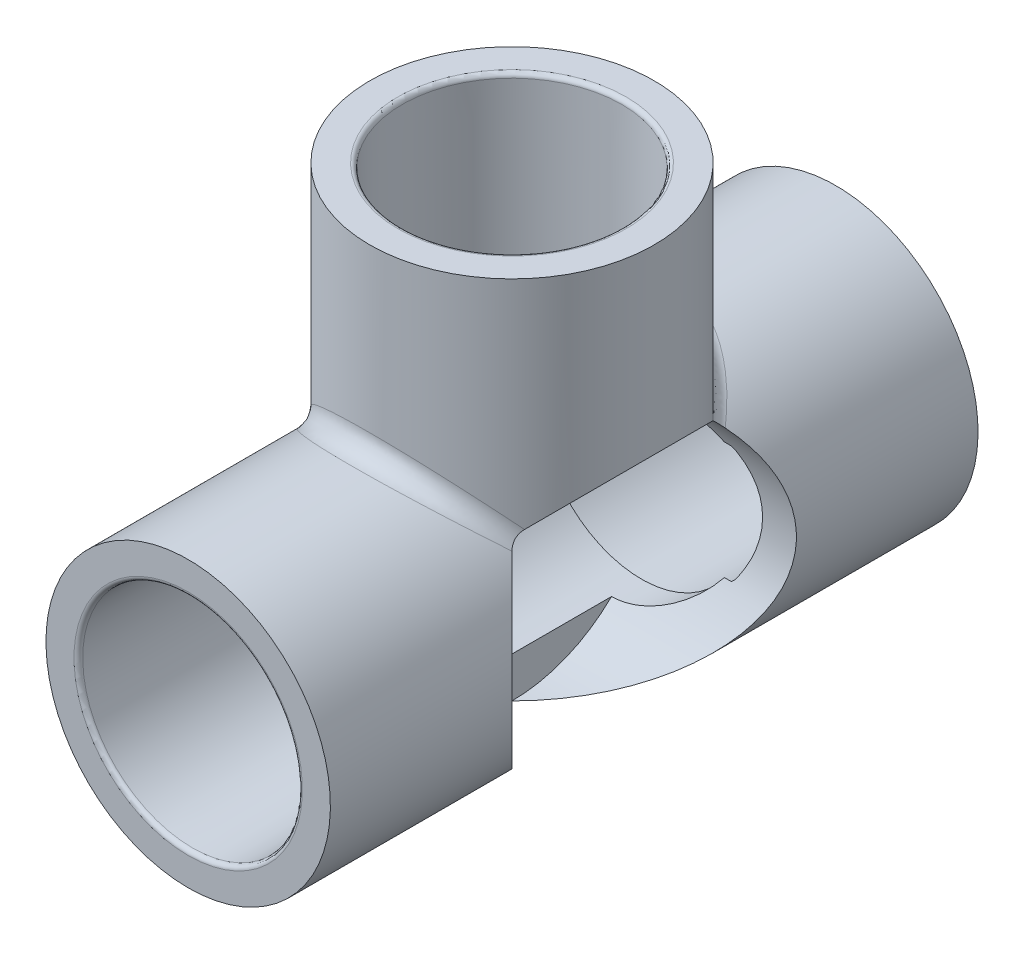
SolidWorks part; units mm, degrees
ref_plane "Front Plane" through (0, 0, 0) normal (0, 0, 1) x (1, 0, 0)
ref_plane "Top Plane" through (0, 0, 0) normal (0, 1, 0) x (1, 0, 0)
ref_plane "Right Plane" through (0, 0, 0) normal (1, 0, 0) x (0, 0, -1)
sketch "Sketch1" plane through (0, 0, 0) normal (1, 0, 0) x (0, 0, -1)
  line L0 (-31.75, 0) -> (31.75, 0) construction
  line L1 (-31.75, 0) -> (-31.75, -13.9446)
  line L2 (-31.75, -13.9446) -> (31.75, -13.9446)
  line L3 (31.75, -13.9446) -> (31.75, 0)
  line L4 (-31.75, -10.7696) -> (-12.7, -10.6172)
  line L5 (-12.7, -10.6172) -> (-12.7, -9.9568)
  line L6 (-12.7, -9.9568) -> (0, -9.9568)
  line L7 (0, -9.9568) -> (0, 0)
  line L8 (0, -9.9568) -> (0, -13.9446) construction
  point P2 (0, 0)
  dimension "Overall Length" = 63.5
  dimension "Diameter 1" = 21.5392
  dimension "Diameter 2" = 21.2344
  dimension "Wall 2" = 3.9878
  dimension "Wall 1" = 3.175
  dimension "Socket Depth" = 19.05
sketch "Sketch2" plane through (0, 0, 0) normal (1, 0, 0) x (0, 0, -1)
  line L0 (0, 0) -> (0, 31.75) construction
  line L1 (0, 31.75) -> (13.9446, 31.75)
  line L2 (13.9446, 31.75) -> (13.9446, 0)
  line L3 (-31.75, 0) -> (31.75, 0) construction
  line L4 (13.9446, 0) -> (0, 0)
  line L5 (10.7696, 31.75) -> (10.6172, 12.7)
  line L6 (10.6172, 12.7) -> (9.9695, 12.7)
  line L7 (9.9695, 12.7) -> (9.9695, 0)
  line L8 (-12.7, -9.9568) -> (0, -9.9568) construction
  dimension "Wall 3" = 3.175
  dimension "D1" = 21.5392
  dimension "D2" = 21.2344
  dimension "D3" = 19.05
  dimension "Diameter 3" = 19.939
sketch "Sketch3" plane through (0, 0, 0) normal (1, 0, 0) x (0, 0, -1)
  line L1 (-31.75, 0) -> (31.75, 0)
  line L2 (-31.75, 0) -> (-31.75, -13.9446)
  line L3 (-31.75, -13.9446) -> (31.75, -13.9446)
  line L4 (31.75, 0) -> (31.75, -13.9446)
revolve "Revolve1" add sketch "Sketch3" angle 360 about L1
sketch "Sketch4" plane through (0, 0, 0) normal (1, 0, 0) x (0, 0, -1)
  line L1 (0, 31.75) -> (13.9446, 31.75)
  line L2 (0, 31.75) -> (0, 0)
  line L3 (0, 0) -> (13.9446, 0)
  line L4 (13.9446, 31.75) -> (13.9446, 0)
revolve "Revolve2" add sketch "Sketch4" angle 360 about L2
sketch "Sketch5" plane through (0, 0, 0) normal (1, 0, 0) x (0, 0, -1)
  line L0 (-12.7, -9.9568) -> (0, -9.9568) construction
  line L1 (-12.7, -10.6172) -> (-12.7, -9.9568) construction
  line L2 (-31.75, -10.7696) -> (-12.7, -10.6172) construction
  line L3 (-12.7, -9.9568) -> (12.7, -9.9568)
  line L4 (-12.7, -10.6172) -> (-12.7, -9.9568)
  line L5 (-31.75, -10.7696) -> (-12.7, -10.6172)
  line L6 (-31.75, -10.7696) -> (-31.75, 0)
  line L7 (-31.75, 0) -> (31.75, 0)
  line L8 (0, 0) -> (0, -9.9568) construction
  line L9 (12.7, -10.6172) -> (12.7, -9.9568)
  line L10 (31.75, -10.7696) -> (12.7, -10.6172)
  line L11 (31.75, -10.7696) -> (31.75, 0)
revolve "Cut-Revolve1" cut sketch "Sketch5" angle 360 about L7
sketch "Sketch6" plane through (0, 0, 0) normal (1, 0, 0) x (0, 0, -1)
  line L0 (9.9695, 0) -> (9.9695, 12.7)
  line L1 (9.9695, 12.7) -> (10.6172, 12.7)
  line L2 (10.7696, 31.75) -> (10.6172, 12.7) construction
  line L3 (10.7696, 31.75) -> (10.6172, 12.7)
  line L4 (0, 0) -> (0, 31.75) construction
  line L5 (0, 0) -> (0, 31.75)
  line L6 (0, 31.75) -> (10.7696, 31.75)
  line L7 (0, 0) -> (9.9695, 0)
revolve "Cut-Revolve2" cut sketch "Sketch6" angle 360 about L5
fillet "Fillet1" radius 0.1619 3 edges at (0, -10.6172, -12.7) (0, 12.7, -10.6172) (0, -10.6172, 12.7)
fillet "Fillet2" radius 0.4308 3 edges at (0, -10.7696, -31.75) (0, 31.75, -10.7696) (0, -10.7696, 31.75)
fillet "Fillet3" radius 1.8536 2 edges at (0, 13.9446, 13.9446) (0, 13.9446, -13.9446)
sketch "Sketch7" plane through (0, 0, 0) normal (1, 0, 0) x (0, 0, -1)
  line L0 (-12.7, -9.9568) -> (0, -9.9568) construction
  line L1 (-12.7, -10.6172) -> (-12.7, -9.9568) construction
  line L2 (-31.75, -10.7696) -> (-12.7, -10.6172) construction
  line L3 (-12.7, -9.9568) -> (12.7, -9.9568)
  line L4 (-12.7, -10.6172) -> (-12.7, -9.9568)
  line L5 (-31.75, -10.7696) -> (-12.7, -10.6172)
  line L6 (0, 0) -> (0, -9.9568) construction
  line L7 (0, 0) -> (-31.75, 0) construction
  line L8 (-12.7, 9.9568) -> (-9.9695, 9.9568)
  line L9 (-12.7, 10.6172) -> (-12.7, 9.9568)
  line L10 (-31.75, 10.7696) -> (-12.7, 10.6172)
  line L11 (10.7696, 31.75) -> (10.6172, 12.7) construction
  line L12 (10.6172, 12.7) -> (9.9695, 12.7) construction
  line L13 (9.9695, 12.7) -> (9.9695, 0) construction
  line L14 (10.7696, 31.75) -> (10.6172, 12.7)
  line L15 (10.6172, 12.7) -> (9.9695, 12.7)
  line L16 (9.9695, 12.7) -> (9.9695, 9.9568)
  line L17 (-9.9695, 12.7) -> (-9.9695, 9.9568)
  line L18 (-10.6172, 12.7) -> (-9.9695, 12.7)
  line L19 (-10.7696, 31.75) -> (-10.6172, 12.7)
  line L20 (12.7, -10.6172) -> (12.7, -9.9568)
  line L21 (31.75, -10.7696) -> (12.7, -10.6172)
  line L22 (12.7, 10.6172) -> (12.7, 9.9568)
  line L23 (31.75, 10.7696) -> (12.7, 10.6172)
  line L24 (9.9695, 9.9568) -> (12.7, 9.9568)
  point P24 (0, 9.9568)
  point P29 (-31.75, -10.7696)
sketch "Sketch8" plane through (0, 0, 0) normal (1, 0, 0) x (0, 0, -1)
  line L3 (-31.75, -13.9446) -> (31.75, -13.9446)
  line L4 (31.75, 13.9446) -> (31.75, -13.9446)
  circle A0 centre (0, 0) radius 13.9446
  dimension "D3" = 27.8892
extrude "Cut-Extrude1" cut sketch "Sketch8" along normal blind 17.78 contours A0
equation "\"D1@Sketch2\"=\"Diameter 1@Sketch1\""
equation "\"D2@Sketch2\"=\"Diameter 2@Sketch1\""
equation "\"D3@Sketch2\"=\"Socket Depth@Sketch1\""
equation "\"D1@Fillet1\"=0.25*(\"Diameter 2@Sketch1\"-\"Diameter 3@Sketch2\")*0.5"
equation "\"D1@Fillet2\"=.02*\"Diameter 1@Sketch1\""
equation "\"D1@Fillet3\"=.075*(\"Diameter 1@Sketch1\"+\"Wall 1@Sketch1\")"
